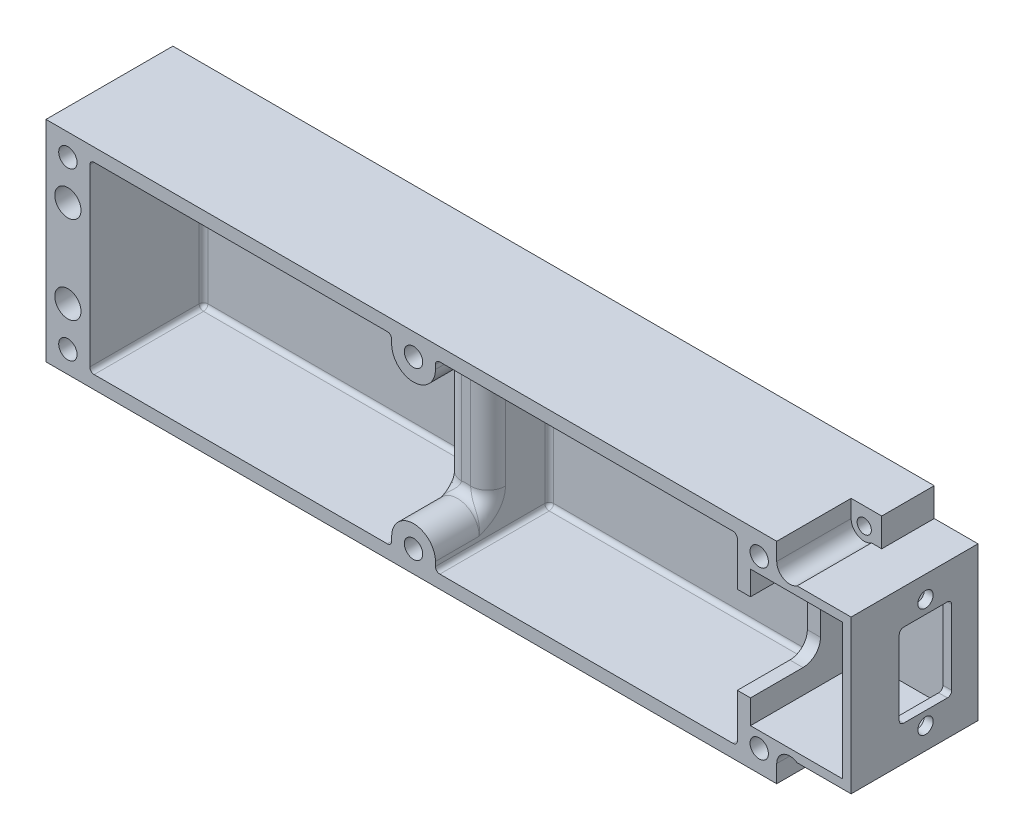
SolidWorks part; units mm, degrees
ref_plane "Top Plane" through (0, 0, 0) normal (0, 0, 1) x (1, 0, 0)
ref_plane "Right Plane" through (0, 0, 0) normal (0, 1, 0) x (1, 0, 0)
ref_plane "Front Plane" through (0, 0, 0) normal (1, 0, 0) x (0, 0, -1)
sketch "Sketch1" plane through (0, 0, 0) normal (0, 0, 1) x (1, 0, 0)
  line L0 (-74, 21) -> (74, -21) construction
  line L1 (-5, 19) -> (-5, -19) construction
  line L2 (5, 19) -> (5, -19) construction
  line L3 (0, 34.0637) -> (0, -29.0623) construction
  line L5 (-74, 21) -> (74, 21) construction
  line L6 (74, 21) -> (74, -21) construction
  line L7 (-74, -21) -> (74, -21) construction
  line L8 (-74, 21) -> (-74, -21) construction
  line L9 (-84, 24) -> (90, 24)
  line L10 (90, 24) -> (90, 17.5)
  line L11 (-84, -24) -> (90, -24)
  line L12 (-84, 24) -> (-84, -24)
  line L13 (90, 17.5) -> (100, 17.5)
  line L14 (100, 17.5) -> (100, -17.5)
  line L15 (-104.1789, 0) -> (137.9248, 0) construction
  line L16 (90, -17.5) -> (100, -17.5)
  line L17 (90, -17.5) -> (90, -24)
  circle A0 centre (0, 19) radius 1.5 construction
  circle A1 centre (0, 19) radius 2.1 construction
  circle A2 centre (0, 19) radius 5 construction
  circle A3 centre (0, -19) radius 5 construction
  circle A4 centre (0, -19) radius 2.1 construction
  circle A5 centre (0, -19) radius 1.5 construction
  circle A6 centre (79, 19) radius 5 construction
  circle A7 centre (-79, 19) radius 5 construction
  circle A8 centre (79, -19) radius 5 construction
  circle A9 centre (-79, -19) radius 5 construction
  circle A10 centre (86, 20) radius 3 construction
  circle A11 centre (86, -20) radius 3 construction
  point P20 (100, 0)
  point P24 (0, 0)
  point P39 (86.3263, 20.0379)
  point P44 (-104.1789, 0)
  point P45 (90, -17.5)
  point P46 (90, -24)
  point P47 (0, 0)
  dimension "D2" = 3
  dimension "D3" = 4.2
  dimension "D7" = 10
  dimension "D9" = 6
  dimension "D1" = 42
  dimension "D5" = 35
  dimension "D6" = 10
  dimension "D4" = 48
  dimension "D8" = 69
  dimension "D10" = 40
  dimension "D11" = 86
  dimension "D12" = 1
extrude "Boss-Extrude1" add sketch "Sketch1" along normal mid plane 3
sketch "Sketch2" plane through (0, 0, 1.5) normal (0, 0, 1) x (1, 0, 0)
  line L4 (74, 21) -> (74, -21) construction
  line L5 (-74, -21) -> (74, -21) construction
  line L6 (-74, 21) -> (-74, -21) construction
  line L7 (-74, 21) -> (74, 21) construction
  line L8 (74, 21) -> (74, -21)
  line L9 (-74, -21) -> (-5, -21)
  line L10 (-74, 21) -> (-74, -21)
  line L11 (-74, 21) -> (-5, 21)
  line L12 (90, 17.5) -> (100, 17.5) construction
  line L13 (100, 17.5) -> (100, -17.5) construction
  line L14 (90, -17.5) -> (100, -17.5) construction
  line L15 (90, -17.5) -> (90, -24) construction
  line L16 (90, 24) -> (90, 17.5) construction
  line L17 (-84, -24) -> (90, -24) construction
  line L18 (-84, 24) -> (-84, -24) construction
  line L19 (-84, 24) -> (90, 24) construction
  line L20 (90, 17.5) -> (100, 17.5)
  line L21 (100, 17.5) -> (100, -17.5)
  line L22 (90, -17.5) -> (100, -17.5)
  line L23 (90, -17.5) -> (90, -24)
  line L24 (90, 24) -> (90, 17.5)
  line L25 (-84, -24) -> (90, -24)
  line L26 (-84, 24) -> (-84, -24)
  line L27 (-84, 24) -> (90, 24)
  line L28 (-5, 19) -> (-5, 21)
  line L29 (5, 19) -> (5, 21)
  line L30 (-5, -19) -> (-5, -21)
  line L31 (5, -19) -> (5, -21)
  line L32 (5, 21) -> (74, 21)
  line L33 (5, -21) -> (74, -21)
  line L34 (-104.1789, 0) -> (137.9248, 0) construction
  line L35 (-104.1789, 0) -> (137.9248, 0) construction
  line L36 (98, -15.5) -> (98, 15.5)
  line L37 (98, 15.5) -> (77, 15.5)
  line L38 (77, 15.5) -> (77, -15.5)
  line L39 (98, -15.5) -> (77, -15.5)
  circle A0 centre (0, 19) radius 5 construction
  circle A1 centre (0, -19) radius 5 construction
  arc A2 (5, -19) -> (-5, -19) centre (0, -19) ccw
  arc A3 (-5, 19) -> (5, 19) centre (0, 19) ccw
  point P31 (77, 0)
  point P32 (98, 0)
  dimension "D3" = 3
  dimension "D1" = 2
  dimension "D2" = 2
extrude "Boss-Extrude2" add sketch "Sketch2" along normal blind 26
sketch "Sketch3" plane through (0, 0, 1.5) normal (0, 0, 1) x (1, 0, 0)
  line L1 (-5, 19) -> (-5, -19)
  line L2 (5, 19) -> (5, -19)
  circle A0 centre (0, -19) radius 5 construction
  circle A1 centre (0, 19) radius 5 construction
  arc A2 (5, -19) -> (-5, -19) centre (0, -19) ccw
  arc A3 (-5, 19) -> (5, 19) centre (0, 19) ccw
extrude "Boss-Extrude3" add sketch "Sketch3" along normal blind 14
sketch "Sketch8" plane through (100, 0, 0) normal (1, 0, 0) x (0, 0, -1)
  line L0 (-16.9, 16) -> (-4.1, -16) construction
  line L1 (-16.9, 16) -> (-4.1, 16) construction
  line L2 (-16.9, 16) -> (-16.9, -16) construction
  line L3 (-16.9, -16) -> (-4.1, -16) construction
  line L4 (-4.1, 16) -> (-4.1, -16) construction
  line L5 (-16.9, 0) -> (-4.1, 0) construction
  line L8 (-16.5, 9.5) -> (-4.5, -9.5) construction
  line L9 (-16.5, 9.5) -> (-4.5, 9.5)
  line L10 (-16.5, 9.5) -> (-16.5, -9.5)
  line L11 (-16.5, -9.5) -> (-4.5, -9.5)
  line L12 (-4.5, 9.5) -> (-4.5, -9.5)
  line L15 (1.5, -17.5) -> (1.5, 17.5) construction
  circle A0 centre (-10.5, 12.5) radius 1.75
  circle A1 centre (-10.5, -12.5) radius 1.75
  point P12 (-10.5, 0)
  dimension "D2" = 3.5
  dimension "D1" = 32
  dimension "D3" = 25
  dimension "D4" = 12.8
  dimension "D5" = 19
  dimension "D6" = 12
  dimension "D7" = 12
extrude "Cut-Extrude3" cut sketch "Sketch8" against normal up to next
sketch "Sketch12" plane through (0, 0, 27.5) normal (0, 0, 1) x (1, 0, 0)
  line L0 (74, 21) -> (74, -21) construction
  line L1 (74, 10) -> (77, 10)
  line L2 (74, 10) -> (74, -10)
  line L3 (74, -10) -> (77, -10)
  line L4 (77, 10) -> (77, -10)
  line L5 (77, 15.5) -> (77, -15.5) construction
  line L6 (-104.1789, 0) -> (137.9248, 0) construction
  point P8 (74, 0)
  point P9 (0, 0)
  dimension "D1" = 20
extrude "Cut-Extrude4" cut sketch "Sketch12" against normal offset from surface (16 mm away) 10 up to face at (39.5, 0, 1.5)
sketch "Sketch13" plane through (0, 0, 27.5) normal (0, 0, 1) x (1, 0, 0)
  circle A0 centre (-79, 19) radius 2.1
  circle A1 centre (-79, -19) radius 2.1
  circle A2 centre (79, 19) radius 2.1
  circle A3 centre (79, -19) radius 2.1
  circle A4 centre (0, -19) radius 2.1 construction
  circle A5 centre (0, 19) radius 2.1 construction
  circle A6 centre (0, -19) radius 2.1
  circle A7 centre (0, 19) radius 2.1
extrude "Cut-Extrude5" cut sketch "Sketch13" against normal through all
sketch "Sketch14" plane through (0, 0, 27.5) normal (0, 0, 1) x (1, 0, 0)
  line L0 (-104.1789, 0) -> (137.9248, 0) construction
  line L1 (-104.1789, 0) -> (137.9248, 0) construction
  line L2 (-79, 19) -> (-79, -19) construction
  line L3 (83, 20) -> (83, 24)
  line L4 (-84, 24) -> (90, 24) construction
  line L5 (83, 24) -> (90, 24)
  line L6 (90, 24) -> (90, 17.5)
  line L7 (90, 17.5) -> (87.6583, 17.5)
  line L8 (90, -17.5) -> (87.6583, -17.5)
  line L9 (90, -24) -> (90, -17.5)
  line L10 (83, -24) -> (90, -24)
  line L11 (83, -20) -> (83, -24)
  circle A0 centre (-79, 10) radius 3
  arc A1 (83, 20) -> (87.6583, 17.5) centre (86, 20) ccw
  arc A2 (83, -20) -> (87.6583, -17.5) centre (86, -20) cw
  circle A3 centre (-79, -10) radius 3
  dimension "D1" = 6
  dimension "D2" = 20
extrude "Cut-Extrude6" cut sketch "Sketch14" against normal offset from surface (17 mm away) 12 up to face at (2.1, 19, -1.5)
sketch "Sketch15" plane through (0, 0, 10.5) normal (0, 0, 1) x (1, 0, 0)
  circle A0 centre (-79, 10) radius 1.625
  circle A1 centre (-79, -10) radius 1.625
  circle A2 centre (86, 20) radius 1.625
  circle A3 centre (86, -20) radius 1.625
  circle A4 centre (-79, 10) radius 3 construction
  point P11 (0, 0)
  dimension "D1" = 3.25
extrude "Cut-Extrude7" cut sketch "Sketch15" against normal through all
fillet "Fillet1" radius 1 16 edges at (39.5, 21, 1.5) (74, 0, 1.5) (39.5, -21, 1.5) (5, 0, 1.5) (-74, 0, 1.5) (-39.5, 21, 1.5) (-5, 0, 1.5) (-39.5, -21, 1.5) (74, -21, 14.5) (74, 21, 14.5) (5, -21, 14.5) (5, 21, 14.5) (-5, 21, 14.5) (-5, -21, 14.5) (-74, -21, 14.5) (-74, 21, 14.5)
fillet "Fillet2" radius 2 2 edges at (0, -14, 15.5) (0, 14, 15.5)
fillet "Fillet3" radius 4 6 edges at (5, -15.6773, 15.766) (5, 15.6773, 15.766) (-5, 15.6773, 15.766) (-5, -15.6773, 15.766) (5, 0, 15.5) (-5, 0, 15.5)
fillet "Fillet4" radius 4 2 edges at (75.5, -10, 11.5) (75.5, 10, 11.5)
fillet "Fillet5" radius 1 4 edges at (99, 9.5, 16.5) (99, 9.5, 4.5) (99, -9.5, 4.5) (99, -9.5, 16.5)
